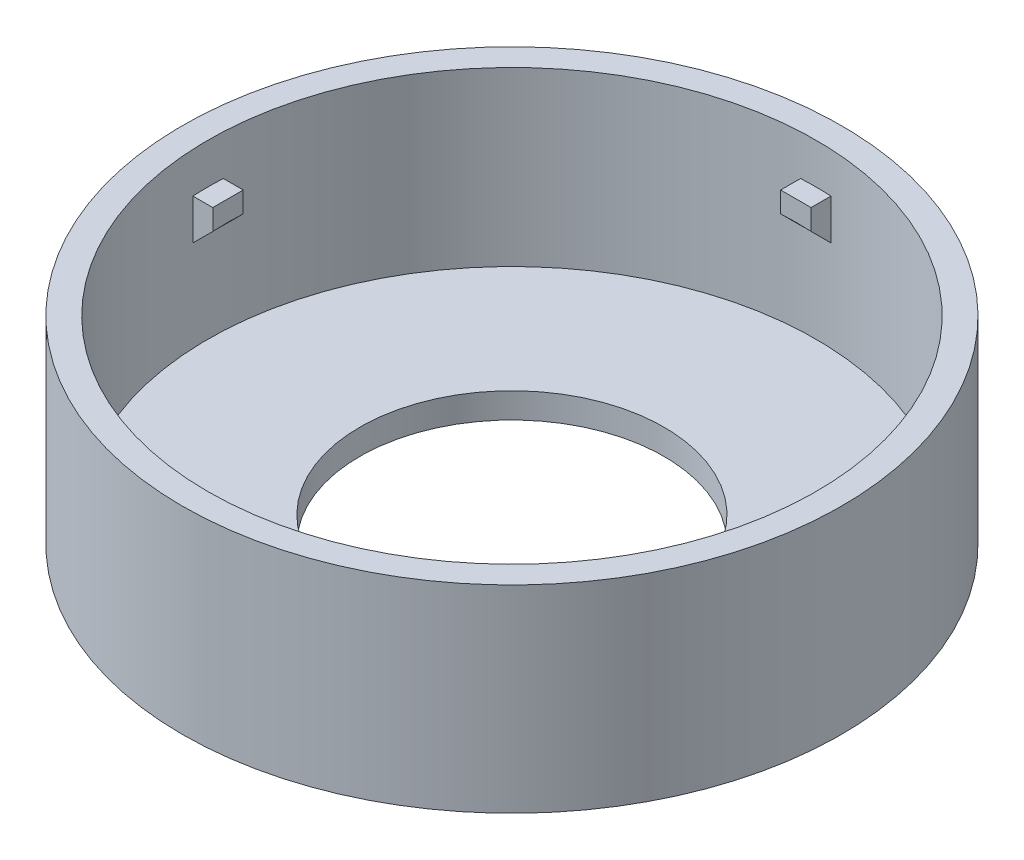
SolidWorks part; units mm, degrees
ref_plane "Front" through (0, 0, 0) normal (0, 0, 1) x (1, 0, 0)
ref_plane "Top" through (0, 0, 0) normal (0, 1, 0) x (1, 0, 0)
ref_plane "Right" through (0, 0, 0) normal (1, 0, 0) x (0, 0, -1)
sketch "Sketch1" plane through (0, 0, 0) normal (0, 1, 0) x (1, 0, 0)
  circle A0 centre (0, 0) radius 32.5
  dimension "D1" = 65
extrude "Boss-Extrude1" add sketch "Sketch1" along normal blind 2.5
sketch "Sketch2" plane through (0, 2.5, 0) normal (0, 1, 0) x (1, 0, 0)
  circle A0 centre (0, 0) radius 30
  circle A1 centre (0, 0) radius 32.5
  circle A2 centre (0, 0) radius 32.5
  dimension "D1" = 0
  dimension "D2" = 2.5
extrude "Boss-Extrude2" add sketch "Sketch2" along normal blind 17
ref_plane "Plane1" through (0, 15.5, 0) normal (0, 1, 0) x (1, 0, 0)
sketch "Sketch3" plane through (0, 15.5, 0) normal (0, 1, 0) x (1, 0, 0)
  line L0 (0, 0) -> (0, 30) construction
  line L1 (1.5, 28) -> (1.5, 30)
  line L2 (-1.5, 28) -> (-1.5, 30)
  line L3 (-1.5, 28) -> (1.5, 28)
  line L4 (-1.5, 0) -> (-1.5, 30) construction
  line L5 (1.5, 0) -> (1.5, 30) construction
  line L6 (28, 1.5) -> (28, -1.5)
  line L7 (28, 1.5) -> (30, 1.5)
  line L8 (28, -1.5) -> (30, -1.5)
  line L9 (1.5, -28) -> (-1.5, -28)
  line L10 (1.5, -28) -> (1.5, -30)
  line L11 (-1.5, -28) -> (-1.5, -30)
  line L12 (-28, -1.5) -> (-28, 1.5)
  line L13 (-28, -1.5) -> (-30, -1.5)
  line L14 (-28, 1.5) -> (-30, 1.5)
  circle A0 centre (0, 0) radius 30 construction
  circle A1 centre (0, 0) radius 30
  point P25 (0, 0)
  dimension "D3" = 2
  dimension "D1" = 1.5
  dimension "D2" = 1.5
  dimension "D4" = 4
extrude "Boss-Extrude3" add sketch "Sketch3" against normal blind 2 contours L1 A1 L2 L3 | L14 A1 L13 L12 | L8 A1 L7 L6 | L11 A1 L10 L9 region at (0, 15.5, -28.9938) region at (28.9938, 15.5, 0) region at (-28.9938, 15.5, 0) region at (0, 15.5, 28.9938)
chamfer "Chamfer1" distance 2 angle 45 4 edges at (0, 13.5, 30) (30, 13.5, 0) (0, 13.5, -30) (-30, 13.5, 0)
sketch "Sketch4" plane through (0, 2.5, 0) normal (0, 1, 0) x (1, 0, 0)
  circle A0 centre (0, 0) radius 15
  dimension "D1" = 30
extrude "Cut-Extrude1" cut sketch "Sketch4" against normal through all
